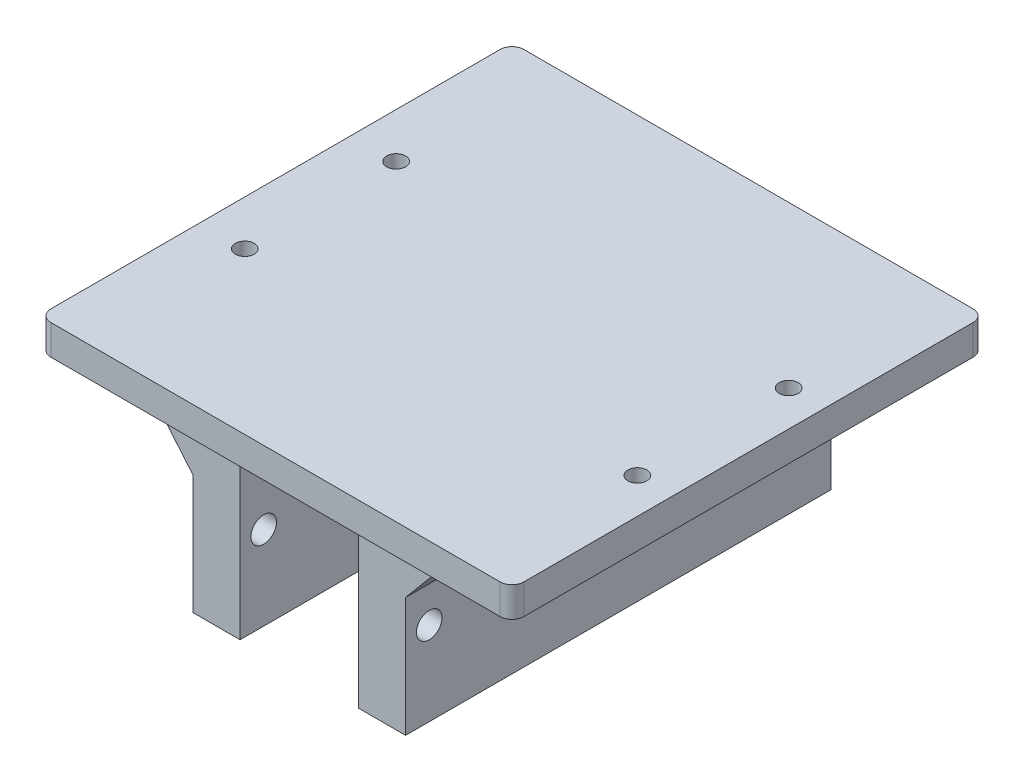
SolidWorks part; units mm, degrees
ref_plane "Front Plane" through (0, 0, 0) normal (0, 0, 1) x (1, 0, 0)
ref_plane "Top Plane" through (0, 0, 0) normal (0, 1, 0) x (1, 0, 0)
ref_plane "Right Plane" through (0, 0, 0) normal (1, 0, 0) x (0, 0, -1)
sketch "Sketch1" plane through (0, 0, 0) normal (0, 1, 0) x (1, 0, 0)
  line L1 (2.5, 0) -> (97.5, 0)
  line L2 (0, 2.5) -> (0, 97.5)
  line L3 (2.5, 100) -> (97.5, 100)
  line L4 (100, 2.5) -> (100, 97.5)
  circle A0 centre (9.5, 34) radius 2
  circle A1 centre (9.5, 66) radius 2
  arc A4 (97.5, 100) -> (100, 97.5) centre (97.5, 97.5) cw
  arc A5 (97.5, 0) -> (100, 2.5) centre (97.5, 2.5) ccw
  arc A6 (2.5, 0) -> (0, 2.5) centre (2.5, 2.5) cw
  arc A7 (0, 97.5) -> (2.5, 100) centre (2.5, 97.5) cw
  circle A8 centre (92.5, 66) radius 2
  circle A9 centre (92.5, 34) radius 2
  point P17 (100, 100)
  point P22 (0, 0)
  point P25 (0, 100)
  dimension "D1" = 4
  dimension "D7" = 2.5
  dimension "D8" = 83
  dimension "D2" = 100
  dimension "D3" = 100
  dimension "D4" = 32
  dimension "D5" = 34
  dimension "D6" = 9.5
extrude "Boss-Extrude1" add sketch "Sketch1" along normal blind 6.35
sketch "Sketch4" plane through (0, 0, 0) normal (0, 1, 0) x (1, 0, 0)
  line L0 (37.5, 50) -> (62.5, 50) construction
  line L1 (27.5, 5) -> (37.5, 5)
  line L2 (27.5, 5) -> (27.5, 95)
  line L3 (27.5, 95) -> (37.5, 95)
  line L4 (37.5, 5) -> (37.5, 95)
  line L5 (62.5, 95) -> (72.5, 95)
  line L6 (62.5, 95) -> (62.5, 5)
  line L7 (62.5, 5) -> (72.5, 5)
  line L8 (72.5, 95) -> (72.5, 5)
  line L9 (50, 100) -> (50, 0) construction
  line L10 (97.5, 100) -> (2.5, 100) construction
  line L11 (2.5, 0) -> (97.5, 0) construction
  point P16 (50, 50)
  point P17 (50, 50)
  dimension "D1" = 25
  dimension "D2" = 5
  dimension "D3" = 10
extrude "Boss-Extrude2" add sketch "Sketch4" against normal blind 36.75
sketch "Sketch5" plane through (27.5, 0, 0) normal (-1, 0, 0) x (0, 0, 1)
  line L0 (-95, -36.75) -> (-95, 0) construction
  line L2 (-95, 0) -> (-5, 0) construction
  circle A0 centre (-90, -19.05) radius 2.7
  circle A1 centre (-50, -19.05) radius 2.7
  circle A2 centre (-10, -19.05) radius 2.7
  dimension "D1" = 40
  dimension "D3" = 5.4
  dimension "D2" = 80
  dimension "D4" = 5
  dimension "D5" = 19.05
extrude "Cut-Extrude1" cut sketch "Sketch5" against normal through all
draft "Draft1" [suppressed] type of draft neutral plane draft angle 5 faces to draft 6 parameters "D1"=5
sketch "Sketch6" plane through (0, 0, -5) normal (0, 0, 1) x (1, 0, 0)
  line L0 (72.5, 0) -> (82.1418, 0)
  line L1 (2.5, 0) -> (97.5, 0) construction
  line L2 (82.1418, 0) -> (72.5, -11.4907)
  line L3 (72.5, -36.75) -> (72.5, 0) construction
  line L4 (72.5, -11.4907) -> (72.5, 0)
  line L5 (27.5, 0) -> (17.8582, 0)
  line L6 (17.8582, 0) -> (27.5, -11.4907)
  line L7 (27.5, -36.75) -> (27.5, 0) construction
  line L8 (27.5, -11.4907) -> (27.5, 0)
  dimension "D1" = 15
  dimension "D2" = 50
extrude "Boss-Extrude3" add sketch "Sketch6" against normal up to surface (90 mm away) from surface up to face at (32.5, -18.375, -95) starting at face at (32.5, -18.375, -5)
